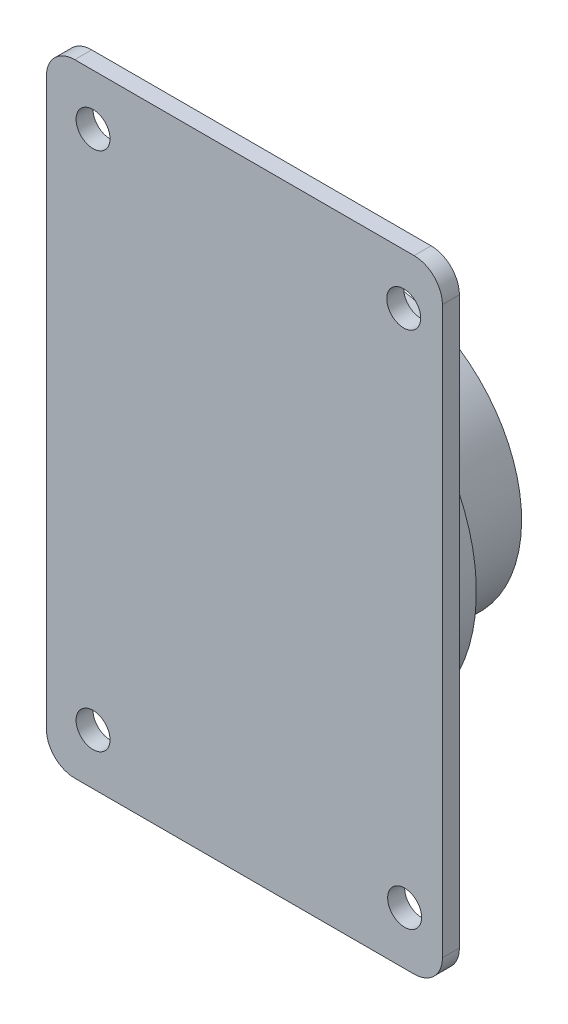
SolidWorks part; units mm, degrees
material "Cast Stainless Steel"
ref_plane "Front Plane" through (0, 0, 0) normal (0, 0, 1) x (1, 0, 0)
ref_plane "Top Plane" through (0, 0, 0) normal (0, 1, 0) x (1, 0, 0)
ref_plane "Right Plane" through (0, 0, 0) normal (1, 0, 0) x (0, 0, -1)
other "Center of Mass"
sketch "Sketch3" plane through (0, 0, 0) normal (0, 1, 0) x (1, 0, 0)
  circle A0 centre (0, 0) radius 25
extrude "Boss-Extrude1" add sketch "Sketch3" against normal blind 15 contours A0
sketch "Sketch4" plane through (0, -15, 0) normal (0, -1, 0) x (1, 0, 0)
  circle A0 centre (0, 0) radius 32
extrude "Boss-Extrude2" add sketch "Sketch4" along normal blind 6
sketch "Sketch6" plane through (0, -21, 0) normal (0, -1, 0) x (1, 0, 0)
  line L1 (35, 0) -> (35, -55)
  line L2 (35, -55) -> (-35, -55)
  line L3 (-35, -55) -> (-35, 55)
  line L4 (-35, 55) -> (35, 55)
  line L5 (35, 55) -> (35, 0)
extrude "Boss-Extrude3" add sketch "Sketch6" along normal blind 3
fillet "Fillet1" radius 5 1 edges at (35, -22.5, 55)
fillet "Fillet2" radius 5 3 edges at (-35, -22.5, 55) (-35, -22.5, -55) (35, -22.5, -55)
sketch "Sketch8" plane through (0, -24, 0) normal (0, -1, 0) x (1, 0, 0)
  circle A0 centre (26.7585, -46) radius 3
  circle A1 centre (-28.159, -46) radius 3
  circle A2 centre (26.7585, 46) radius 3
  circle A3 centre (-28.3209, 45.6631) radius 3
extrude "Cut-Extrude1" cut sketch "Sketch8" against normal blind 3 contours A3 | A2 | A1 | A0
ref_axis "Axis1" through (0, -15, 0) along (0, 1, 0)
ref_point "Point1"
move or copy body "Body-Move/Copy1" bodies to move or copy 106 copy no rotation origin (0, 0, 0) rotation axis (-0.5774, -0.5774, 0.5774) rotation angle 120
ref_axis "Axis2" through (0, 0, 15) along (0, 0, -1)
ref_point "Point2"
move or copy body "Body-Move/Copy2" bodies to move or copy 107 copy no translate (0, 0, -24)
ref_plane "Plane2" through (0, 0, -99) normal (0, 0, -1) x (-1, 0, 0)
ref_axis "Axis3" through (0, 0, -9) along (0, 0, -1)
ref_point "Point3"
move or copy body "Body-Move/Copy3" bodies to move or copy 108 copy no translate (0, 0, 99)
move or copy body "Body-Move/Copy4" bodies to move or copy 109 copy no rotation origin (0, 0, 0) rotation axis (0, 0, 1) rotation angle 90
